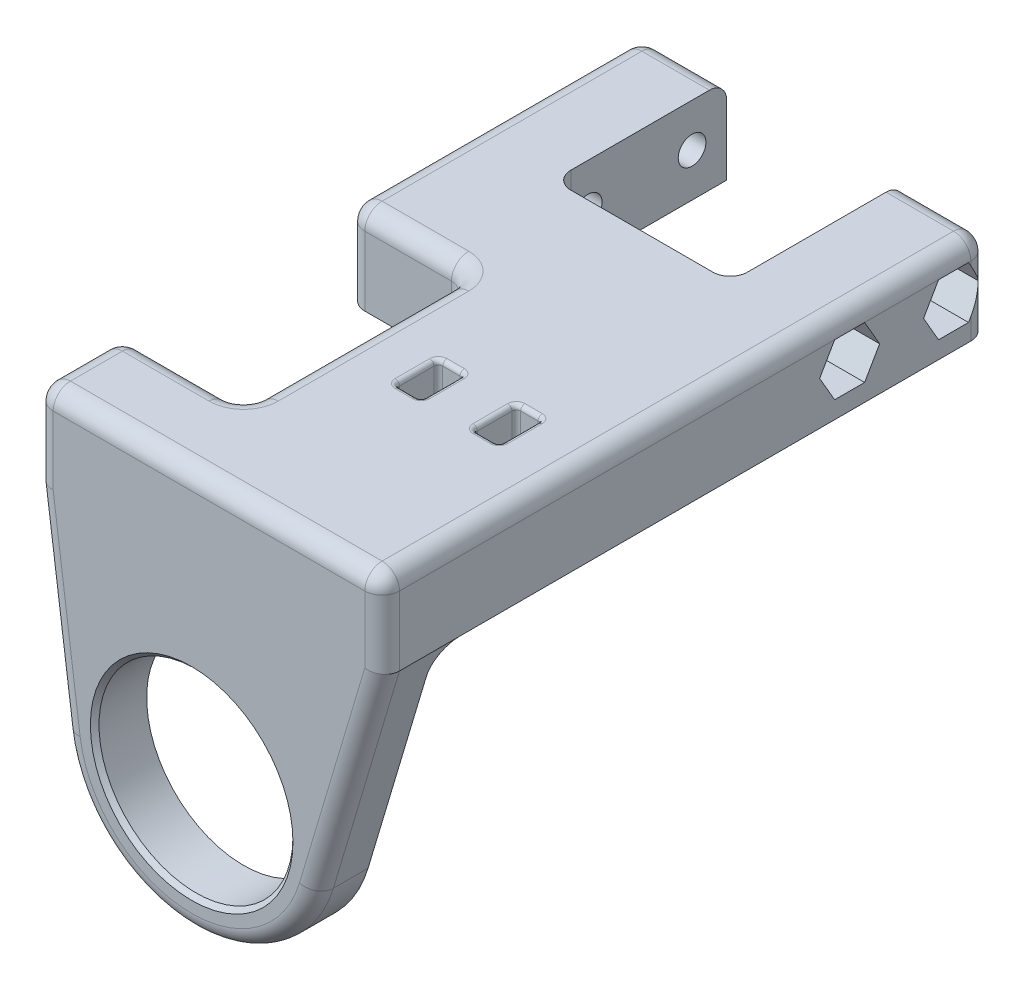
SolidWorks part; units mm, degrees
ref_plane "Top Plane" through (0, 0, 0) normal (0, 0, 1) x (1, 0, 0)
ref_plane "Right Plane" through (0, 0, 0) normal (0, 1, 0) x (1, 0, 0)
ref_plane "Front Plane" through (0, 0, 0) normal (1, 0, 0) x (0, 0, -1)
sketch "Sketch1" plane through (0, 0, 0) normal (0, 0, 1) x (1, 0, 0)
  line L0 (0, 0) -> (0, 31.25) construction
  line L1 (22, 31.25) -> (22, 21.25)
  line L2 (-18, 31.25) -> (22, 31.25)
  line L3 (-18, 31.25) -> (-18, 21.25)
  line L4 (22, 21.25) -> (14.3729, -4.2919)
  line L5 (-18, 21.25) -> (-14.8656, -2.0038)
  line L6 (-18, 21.25) -> (22, 21.25) construction
  arc A0 (-14.8656, -2.0038) -> (14.3729, -4.2919) centre (0, 0) ccw construction
  circle A1 centre (0, 0) radius 11 construction
  circle A2 centre (0, 0) radius 4 construction
  arc A3 (-14.8656, -2.0038) -> (14.3729, -4.2919) centre (0, 0) ccw
  dimension "D1" = 30
  dimension "D2" = 22
  dimension "D3" = 8
  dimension "D6" = 10
  dimension "D4" = 21.25
  dimension "D5" = 40
  dimension "D7" = 18
extrude "Boss-Extrude1" add sketch "Sketch1" along normal blind 6
sketch "Sketch2" plane through (0, 0, 6) normal (0, 0, 1) x (1, 0, 0)
  circle A2 centre (0, 0) radius 11.2
  circle A3 centre (0, 0) radius 11.2
  dimension "D1" = 0.2
extrude "Cut-Extrude1" cut sketch "Sketch2" against normal through all
sketch "Sketch3" plane through (0, 0, 0) normal (0, 0, -1) x (-1, 0, 0)
  line L0 (18, 31.25) -> (-22, 31.25) construction
  line L1 (-22, 31.25) -> (-12, 31.25) construction
  line L2 (-22, 31.25) -> (-22, 21.25) construction
  line L3 (-22, 21.25) -> (-12, 21.25) construction
  line L4 (-12, 31.25) -> (-12, 21.25) construction
  line L5 (8, 31.25) -> (18, 31.25) construction
  line L6 (8, 31.25) -> (8, 21.25) construction
  line L7 (8, 21.25) -> (18, 21.25) construction
  line L8 (18, 31.25) -> (18, 21.25) construction
  line L9 (-12, 26.25) -> (8, 26.25) construction
  line L11 (-2, 26.25) -> (-2, 31.25) construction
  line L13 (-22, 31.25) -> (18, 31.25)
  line L14 (-22, 31.25) -> (-22, 21.25)
  line L15 (-22, 21.25) -> (18, 21.25)
  line L16 (18, 31.25) -> (18, 21.25)
  point P12 (-2, 26.25)
  dimension "D1" = 20
extrude "Boss-Extrude2" add sketch "Sketch3" along normal blind 44
sketch "Sketch4" plane through (0, 0, -44) normal (0, 0, -1) x (-1, 0, 0)
  line L0 (-22, 21.25) -> (18, 21.25) construction
  line L1 (-22, 31.25) -> (-12.2, 31.25)
  line L2 (-22, 31.25) -> (-22, 21.25)
  line L3 (-22, 21.25) -> (-12.2, 21.25)
  line L4 (-12.2, 31.25) -> (-12.2, 21.25)
  line L5 (8.2, 31.25) -> (18, 31.25)
  line L6 (8.2, 31.25) -> (8.2, 21.25)
  line L7 (8.2, 21.25) -> (18, 21.25)
  line L8 (18, 31.25) -> (18, 21.25)
  line L9 (-12, 31.25) -> (-12, 21.25) construction
  line L10 (8, 31.25) -> (8, 21.25) construction
  line L11 (18, 31.25) -> (-22, 31.25) construction
  dimension "D1" = 0.2
  dimension "D2" = 0.2
extrude "Boss-Extrude3" add sketch "Sketch4" along normal blind 20
fillet "Fillet1" radius 3 1 edges at (2, 21.25, 0)
sketch "Sketch5" plane through (12.2, 0, 0) normal (-1, 0, 0) x (0, 0, 1)
  line L0 (-64, 26.25) -> (-44, 26.25) construction
  line L1 (-64, 21.25) -> (-64, 31.25) construction
  line L2 (-44, 21.25) -> (-44, 31.25) construction
  line L3 (-54, 31.25) -> (-54, 26.25) construction
  line L4 (-64, 31.25) -> (-44, 31.25) construction
  circle A0 centre (-60, 26.25) radius 1.75
  circle A1 centre (-48, 26.25) radius 1.75
  dimension "D1" = 3.5
  dimension "D2" = 12
hole_wizard "CBORE for M3 Hex Socket Head Cap Screw1" positions "Sketch6" profile "Sketch7" counterbore size "M3" standard "ISO" end condition through all
sketch "Sketch6" plane through (-18, 0, 0) normal (-1, 0, 0) x (0, 0, 1)
  point P0 (-60, 26.25)
  point P3 (-48, 26.25)
sketch "Sketch7" plane through (-18, 26.25, -60) normal (0, 1, 0) x (0, 0, 1)
  line L0 (0, 0) -> (0, 40)
  line L1 (0, 40) -> (1.6, 40)
  line L3 (1.6, 40) -> (1.6, 3.4)
  line L4 (1.6, 3.4) -> (3.25, 3.4)
  line L5 (3.25, 3.4) -> (3.25, 0)
  line L7 (3.25, 0) -> (0, 0)
  line L11 (0, -6.35) -> (0, 107.95) construction
  dimension "Thru Hole Dia." = 3.2
  dimension "Thru Hole Depth" = 40
  dimension "C'Bore Dia." = 6.5
  dimension "C'Bore Depth" = 3.4
sketch "Sketch8" plane through (22, 0, 0) normal (1, 0, 0) x (0, 0, -1)
  line L1 (49.7321, 29.25) -> (46.2679, 29.25)
  line L2 (46.2679, 29.25) -> (44.5359, 26.25)
  line L3 (44.5359, 26.25) -> (46.2679, 23.25)
  line L4 (46.2679, 23.25) -> (49.7321, 23.25)
  line L5 (49.7321, 23.25) -> (51.4641, 26.25)
  line L6 (51.4641, 26.25) -> (49.7321, 29.25)
  line L7 (58.2679, 29.25) -> (56.5359, 26.25)
  line L8 (56.5359, 26.25) -> (58.2679, 23.25)
  line L9 (58.2679, 23.25) -> (61.7321, 23.25)
  line L10 (61.7321, 23.25) -> (63.4641, 26.25)
  line L11 (63.4641, 26.25) -> (61.7321, 29.25)
  line L12 (61.7321, 29.25) -> (58.2679, 29.25)
  circle A0 centre (48, 26.25) radius 3 construction
  circle A1 centre (60, 26.25) radius 3 construction
  dimension "D1" = 6
extrude "Cut-Extrude3" cut sketch "Sketch8" against normal offset from surface (5.8 mm away) 4 up to face at (12.2, 27.85, -60)
sketch "Sketch9" plane through (0, 31.25, 0) normal (0, 1, 0) x (1, 0, 0)
  line L0 (-18, -6) -> (-18, 64) construction
  line L1 (-18, 30) -> (-4, 30)
  line L2 (-18, 30) -> (-18, 4)
  line L3 (-18, 4) -> (-4, 4)
  line L4 (-4, 30) -> (-4, 4)
  line L5 (22, -6) -> (-18, -6) construction
  dimension "D1" = 36
  dimension "D2" = 10
  dimension "D3" = 14
extrude "Cut-Extrude4" cut sketch "Sketch9" against normal through all
sketch "Sketch10" plane through (0, 31.25, 0) normal (0, 1, 0) x (1, 0, 0)
  line L0 (9, 23.4892) -> (9, 10.5108) construction
  line L1 (3, 19.5) -> (6, 19.5)
  line L2 (3, 19.5) -> (3, 14.5)
  line L3 (3, 14.5) -> (6, 14.5)
  line L4 (6, 19.5) -> (6, 14.5)
  line L5 (12, 19.5) -> (12, 14.5)
  line L6 (15, 14.5) -> (12, 14.5)
  line L7 (15, 19.5) -> (15, 14.5)
  line L8 (15, 19.5) -> (12, 19.5)
  line L9 (3, 17) -> (15, 17) construction
  line L10 (-4, 17) -> (9, 17) construction
  line L11 (-4, 4) -> (-4, 30) construction
  line L12 (-4, 10.5108) -> (22, 10.5108) construction
  line L13 (22, -6) -> (22, 64) construction
  point P10 (9, 17)
  point P21 (0, 0)
  dimension "D1" = 3
  dimension "D2" = 5
  dimension "D3" = 6
fillet "Fillet2" radius 2 2 edges at (-4, 26.25, -4) (-4, 26.25, -30)
fillet "Fillet3" radius 2 2 edges at (12.2, 26.25, -44) (-8.2, 26.25, -44)
fillet "Fillet4" radius 2 9 edges at (-16.4328, 9.6231, 6) (-1.1703, -14.9543, 6) (18.1864, 8.479, 6) (-18, 26.25, 6) (22, 26.25, 6) (-18, 26.25, -4) (-18, 26.25, -30) (22, 26.25, -64) (-18, 26.25, -64)
fillet "Fillet5" radius 2 17 edges at (-12.1, 31.25, -64) (-17.4142, 31.25, -63.4142) (-18, 31.25, -47) (-17.4142, 31.25, -30.5858) (-11, 31.25, -30) (-4.5858, 31.25, -29.4142) (-4, 31.25, -17) (-4.5858, 31.25, -4.5858) (-11, 31.25, -4) (-17.4142, 31.25, -3.4142) (-18, 31.25, 1) (-17.4142, 31.25, 5.4142) (2, 31.25, 6) (21.4142, 31.25, 5.4142) (16.1, 31.25, -64) (21.4142, 31.25, -63.4142) (22, 31.25, -29)
chamfer "Chamfer1" distance 0.5 angle 45 1 edges at (11.2, 0, 6)
extrude "Cut-Extrude5" cut sketch "Sketch10" against normal up to next
fillet "Fillet6" radius 0.5 24 edges at (13.5, 21.25, -14.5) (13.5, 31.25, -14.5) (13.5, 31.25, -19.5) (13.5, 21.25, -19.5) (4.5, 21.25, -14.5) (4.5, 31.25, -14.5) (4.5, 31.25, -19.5) (4.5, 21.25, -19.5) (15, 26.25, -19.5) (15, 31.25, -17) (15, 26.25, -14.5) (15, 21.25, -17) (12, 26.25, -14.5) (12, 31.25, -17) (12, 26.25, -19.5) (12, 21.25, -17) (6, 26.25, -19.5) (6, 31.25, -17) (6, 26.25, -14.5) (6, 21.25, -17) (3, 26.25, -14.5) (3, 31.25, -17) (3, 26.25, -19.5) (3, 21.25, -17)
